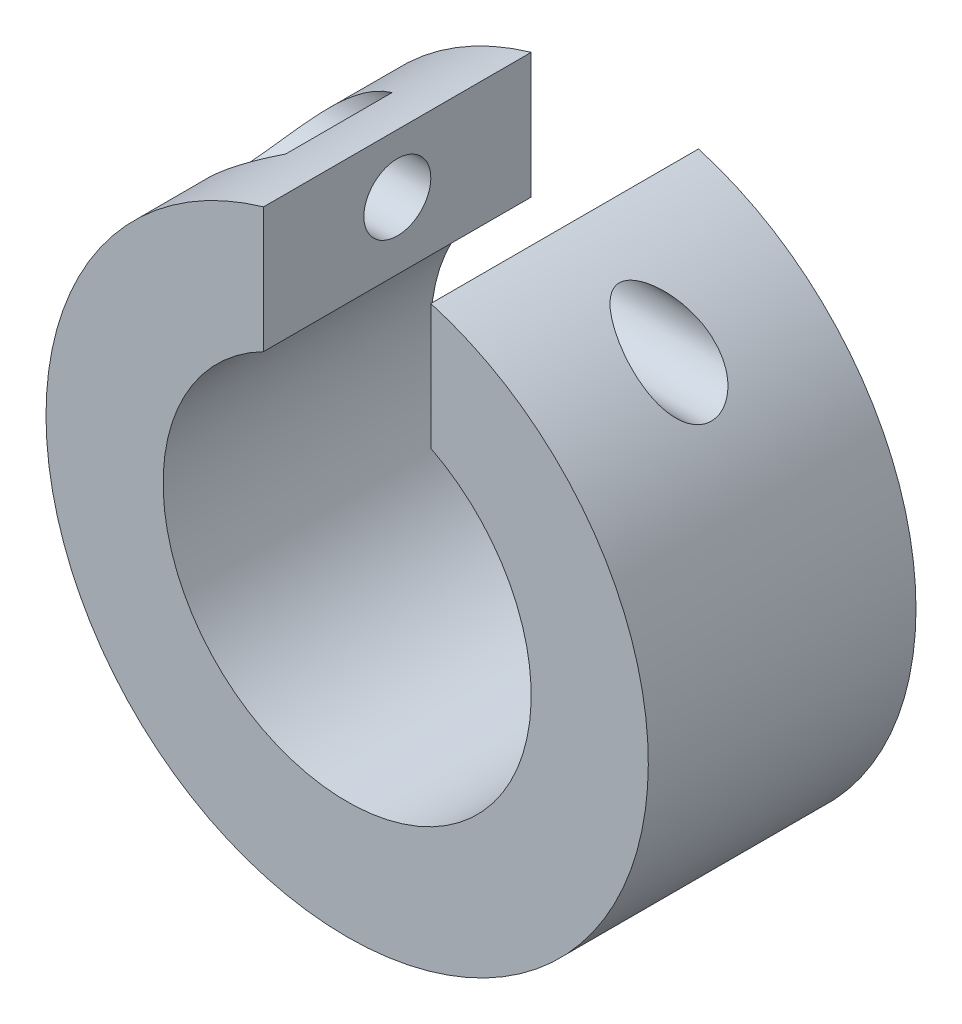
SolidWorks part; units mm, degrees
ref_plane "Plan de face" through (0, 0, 0) normal (0, 0, 1) x (1, 0, 0)
ref_plane "Plan de dessus" through (0, 0, 0) normal (0, 1, 0) x (1, 0, 0)
ref_plane "Plan de droite" through (0, 0, 0) normal (1, 0, 0) x (0, 0, -1)
sketch "Esquisse1" plane through (0, 0, 0) normal (0, 0, 1) x (1, 0, 0)
  circle A0 centre (0, 0) radius 5.5
  circle A1 centre (0, 0) radius 9
  dimension "D1" = 11
  dimension "D2" = 18
extrude "Boss.-Extru.1" add sketch "Esquisse1" along normal blind 8
sketch "Esquisse2" plane through (0, 0, 8) normal (0, 0, 1) x (1, 0, 0)
  line L1 (2.5, 3) -> (-2.5, 3)
  line L2 (2.5, 3) -> (2.5, 11)
  line L3 (2.5, 11) -> (-2.5, 11)
  line L4 (-2.5, 3) -> (-2.5, 11)
  dimension "D1" = 8
  dimension "D2" = 5
  dimension "D3" = 2.5
  dimension "D4" = 3
extrude "Enlèv. mat.-Extru.1" cut sketch "Esquisse2" against normal up to next
sketch "Esquisse8" plane through (-2.5, 0, 0) normal (1, 0, 0) x (0, 0, -1)
  line L0 (-8, 8.6458) -> (-8, 4.899) construction
  line L2 (0, 8.6458) -> (-8, 8.6458) construction
  circle A0 centre (-4, 6.8958) radius 1
  dimension "D1" = 2
  dimension "D2" = 4
  dimension "D3" = 1.75
extrude "Enlèv. mat.-Extru.2" cut sketch "Esquisse8" against normal up to next
ref_plane "Plan1" through (7, 0, 0) normal (-1, 0, 0) x (0, 0, 1)
hole_wizard "Dégagement M21" positions "Esquisse19" profile "Esquisse20" hole size "M2" standard "ISO" end condition up to next
sketch "Esquisse19" plane through (7, 0, 0) normal (-1, 0, 0) x (0, 0, 1)
  point P0 (4, 6.8958)
sketch "Esquisse20" plane through (7, 6.8958, 4) normal (0, 1, 0) x (0, 0, -1)
  line L0 (0, 0) -> (0, 4.5)
  line L1 (0, 4.5) -> (1.1, 4.5)
  line L2 (1.1, 4.5) -> (1.1, 0)
  line L5 (1.1, 0) -> (0, 0)
  line L11 (0, -6.35) -> (0, 107.95) construction
  dimension "Diamètre du perçage jusqu'au prochain" = 2.2
  dimension "Profondeur du perçage jusqu'au prochain" = 4.5
ref_plane "Plan2" through (-7, 0, 0) normal (1, 0, 0) x (0, 0, -1)
sketch "Esquisse21" plane through (-7, 0, 0) normal (1, 0, 0) x (0, 0, -1)
  circle A0 centre (-4, 6.8958) radius 1.9
  dimension "D1" = 3.8
extrude "Enlèv. mat.-Extru.4" cut sketch "Esquisse21" along normal blind 2.75 and the other way blind 2.75 contours A0
equation "\"D2@Esquisse8\"=\"D1@Boss.-Extru.1\"/2"
equation "\"D3@Esquisse8\"=(\"D2@Esquisse1\"-\"D1@Esquisse1\")/4"
